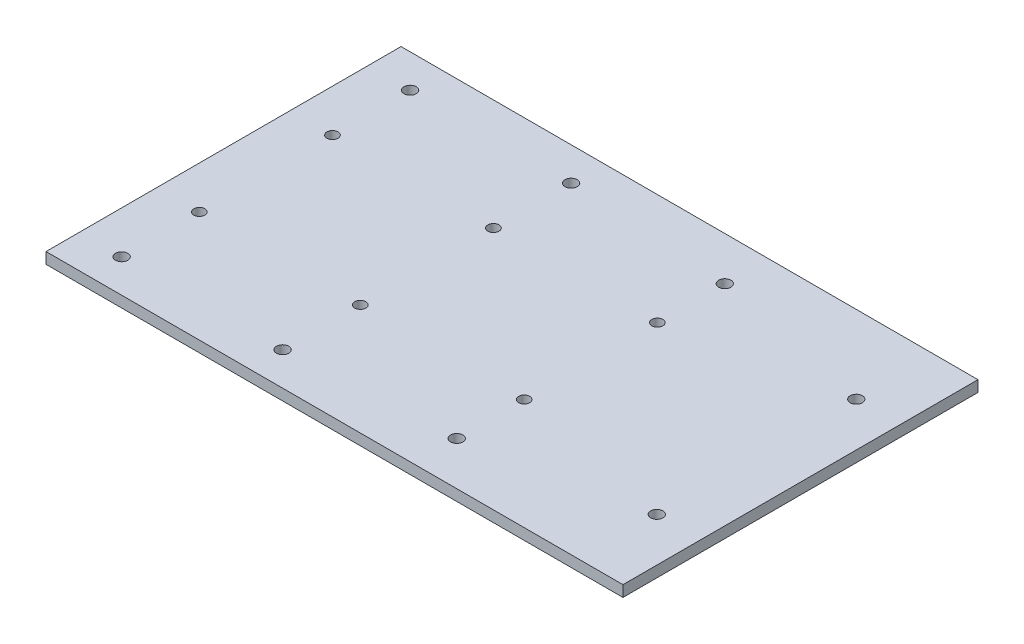
SolidWorks part; units mm, degrees
material "6061-T6 (SS)"
ref_plane "Front Plane" through (0, 0, 0) normal (0, 0, 1) x (1, 0, 0)
ref_plane "Top Plane" through (0, 0, 0) normal (0, 1, 0) x (1, 0, 0)
ref_plane "Right Plane" through (0, 0, 0) normal (1, 0, 0) x (0, 0, -1)
sketch "Sketch1" plane through (0, 0, 0) normal (0, 1, 0) x (1, 0, 0)
  line L1 (-165.1, -101.6) -> (165.1, -101.6)
  line L2 (-165.1, -101.6) -> (-165.1, 101.6)
  line L3 (-165.1, 101.6) -> (165.1, 101.6)
  line L4 (165.1, -101.6) -> (165.1, 101.6)
  line L5 (-165.1, -101.6) -> (165.1, 101.6) construction
  line L6 (-165.1, 101.6) -> (165.1, -101.6) construction
  point P0 (0, 0)
  dimension "D1" = 330.2
  dimension "D2" = 203.2
extrude "Boss-Extrude1" add sketch "Sketch1" along normal blind 6.35
sketch "Sketch2" plane through (0, 6.35, 0) normal (0, 1, 0) x (1, 0, 0)
  line L0 (-140.8516, 82.55) -> (-140.8516, -82.55) construction
  line L1 (-48.7159, 82.55) -> (-48.7159, -82.55) construction
  line L2 (45.0841, 76.701) -> (45.0841, -76.699) construction
  line L3 (-140.8516, 0) -> (45.0841, 0.001) construction
  line L4 (-140.8514, -38.1) -> (45.0843, -38.099) construction
  line L5 (-140.8518, 38.1) -> (45.0839, 38.101) construction
  point P0 (-140.8516, -82.55)
  point P1 (-48.7159, -82.55)
  point P3 (45.0841, -76.699)
  point P5 (45.0841, 76.701)
  point P7 (-48.7159, 82.55)
  point P9 (-140.8516, 82.55)
  point P25 (-48.7159, -38.0995)
  point P26 (-140.8514, -38.1)
  point P27 (-48.7159, 38.1005)
  point P28 (45.0839, 38.101)
  point P29 (45.0843, -38.099)
  point P30 (-140.8518, 38.1)
  point P31 (139.9541, 57.072)
  point P32 (139.9541, -57.072)
  dimension "D1" = 38.1
  dimension "D2" = 38.1
hole_wizard "1/4 (0.25) Press Dowel Hole1" positions "Sketch3" profile "Sketch4" hole size "1/4" standard "ANSI Inch" end condition through all
sketch "Sketch3" plane through (0, 6.35, 0) normal (0, 1, 0) x (1, 0, 0)
  point P0 (-140.8518, 38.1)
  point P3 (-140.8514, -38.1)
  point P6 (-48.7159, -38.0995)
  point P9 (-48.7159, 38.1005)
  point P12 (45.0839, 38.101)
  point P15 (45.0843, -38.099)
sketch "Sketch4" plane through (-140.8518, 6.35, -38.1) normal (1, 0, 0) x (0, 0, 1)
  line L0 (0, 0) -> (0, 6.35)
  line L1 (0, 6.35) -> (3.175, 6.35)
  line L2 (3.175, 6.35) -> (3.175, 0)
  line L5 (3.175, 0) -> (0, 0)
  line L11 (0, -6.35) -> (0, 107.95) construction
  dimension "Thru Hole Dia." = 6.35
  dimension "Thru Hole Depth" = 6.35
hole_wizard "M8x1.0 Tapped Hole1" positions "Sketch5" profile "Sketch6" tap size "M8x1.0" standard "ANSI Metric" end condition through all
sketch "Sketch5" plane through (0, 6.35, 0) normal (0, 1, 0) x (1, 0, 0)
  point P0 (-140.8516, 82.55)
  point P3 (-48.7159, 82.55)
  point P6 (45.0841, 76.701)
  point P9 (45.0841, -76.699)
  point P12 (-48.7159, -82.55)
  point P15 (-140.8516, -82.55)
  point P19 (139.9541, 57.072)
  point P22 (139.9541, -57.072)
sketch "Sketch6" plane through (-140.8516, 6.35, -82.55) normal (1, 0, 0) x (0, 0, 1)
  line L0 (0, 0) -> (0, 6.35)
  line L1 (0, 6.35) -> (3.5, 6.35)
  line L2 (3.5, 6.35) -> (3.5, 0)
  line L5 (3.5, 0) -> (0, 0)
  line L11 (0, -6.35) -> (0, 107.95) construction
  dimension "Thread Major Dia." = 7
  dimension "Thru Tap Drill Depth" = 6.35
sketch "Sketch7" plane through (0, 6.35, 0) normal (0, 1, 0) x (1, 0, 0)
  line L0 (-165.1, -101.6) -> (165.1, -101.6) construction
  line L1 (-165.1, -101.6) -> (165.1, -101.6) construction
  line L2 (-165.1, -98.425) -> (45.0841, -98.425) construction
  line L3 (-165.1, -92.075) -> (45.0841, -92.075) construction
  line L4 (-165.1, -85.725) -> (45.0841, -85.725) construction
  line L5 (-165.1, -79.375) -> (45.0841, -79.375) construction
  line L6 (-165.1, -73.025) -> (45.0841, -73.025) construction
  line L7 (-165.1, -66.675) -> (45.0841, -66.675) construction
  line L8 (45.0841, -101.6) -> (45.0841, -54.5996) construction
  line L9 (57.7841, -101.6) -> (57.7841, -54.5996) construction
  line L10 (57.7841, -66.675) -> (165.1, -66.675) construction
  line L11 (57.7841, -73.025) -> (165.1, -73.025) construction
  line L12 (57.7841, -79.375) -> (165.1, -79.375) construction
  line L13 (57.7841, -85.725) -> (165.1, -85.725) construction
  line L14 (57.7841, -92.075) -> (165.1, -92.075) construction
  line L15 (57.7841, -98.425) -> (165.1, -98.425) construction
  line L16 (-165.1, -98.425) -> (165.1, -98.425) construction
  line L17 (57.7841, -60.325) -> (165.1, -60.325) construction
  text T0 "JOHN TALIK" font "OLF SimpleSansOC" height 3.175
  text T1 "JAMES LUCE" font "OLF SimpleSansOC" height 3.175
  text T2 "MIMI SHANG" font "OLF SimpleSansOC" height 3.175
  text T3 "JOHNNY FREOLICH" font "OLF SimpleSansOC" height 3.175
  text T4 "JORDEN ROLAND " font "OLF SimpleSansOC" height 3.175
  text T5 "RAWAND RASHEED" font "OLF SimpleSansOC" height 3.175
  text T6 "2017 PSAS PUMP BOIS:" font "OLF SimpleSansOC" height 4.445
  dimension "D1" = 3.175
  dimension "D3" = 12.7
  dimension "D4" = 6.35
  dimension "D2" = 6
